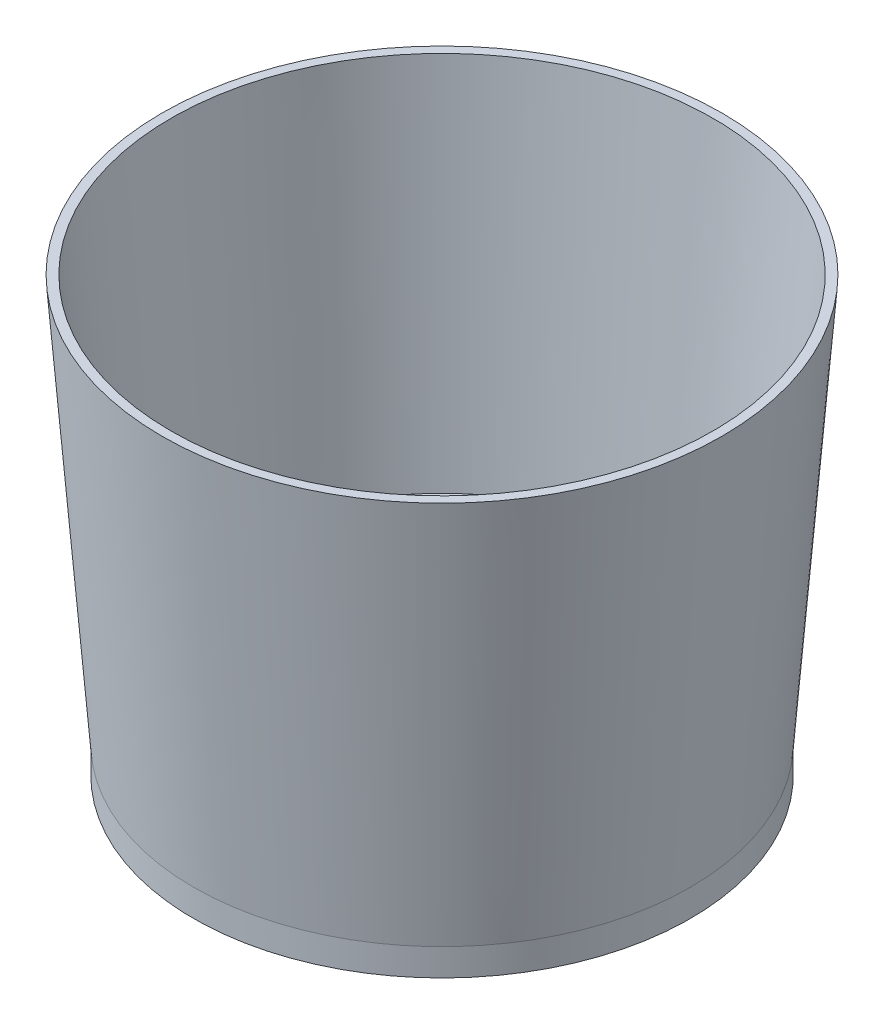
SolidWorks part; units mm, degrees
note: The reader was unsure of these and kept them because the rebuilt part matched: shared geometry of "Sketch3<4>", "Sketch1<4>".
ref_plane "Front Plane" through (0, 0, 0) normal (0, 0, 1) x (1, 0, 0)
ref_plane "Top Plane" through (0, 0, 0) normal (0, 1, 0) x (1, 0, 0)
ref_plane "Right Plane" through (0, 0, 0) normal (1, 0, 0) x (0, 0, -1)
sketch "Sketch1" plane through (0, 0, 0) normal (0, 1, 0) x (1, 0, 0)
  circle A0 centre (0, 0) radius 26.5
  circle A1 centre (0, 0) radius 25.5 construction
  circle A2 centre (0, 0) radius 27.5
  dimension "D1" = 53
  dimension "D2" = 51
  dimension "D3" = 55
ref_plane "Plane1" through (0, 45, 0) normal (0, 1, 0) x (1, 0, 0)
sketch "Sketch3" plane through (0, 45, 0) normal (0, 1, 0) x (1, 0, 0)
  circle A0 centre (0, 0) radius 30
  circle A1 centre (0, 0) radius 31
  dimension "D1" = 60
  dimension "D2" = 62
loft "Loft1" add section "Sketch1" section "Sketch3"
loft "Cut-Loft1" cut section "Sketch3<4>" section "Sketch1<4>"
sketch "Sketch3<4>" plane through (0, 45, 0) normal (0, 1, 0) x (1, 0, 0) same geometry as "Sketch3"
sketch "Sketch1<4>" plane through (0, 0, 0) normal (0, 1, 0) x (1, 0, 0) same geometry as "Sketch1"
sketch "Sketch4" plane through (0, 0, 0) normal (0, -1, 0) x (1, 0, 0)
  circle A0 centre (0, 0) radius 27.5
  circle A1 centre (0, 15) radius 1.5
  circle A2 centre (15, 0) radius 1.5
  circle A3 centre (0, -15) radius 1.5
  circle A4 centre (-15, 0) radius 1.5
  point P15 (0, 0)
  dimension "D1" = 55
  dimension "D2" = 3
  dimension "D4" = 15
  dimension "D3" = 4
extrude "Boss-Extrude1" add sketch "Sketch4" along normal blind 3
sketch "Sketch6" plane through (0, 0, 0) normal (0, 1, 0) x (1, 0, 0)
  circle A0 centre (0, 0) radius 25.5
  circle A1 centre (0, 15) radius 1.5
  circle A2 centre (15, 0) radius 1.5
  circle A3 centre (0, -15) radius 1.5
  circle A4 centre (-15, 0) radius 1.5
  point P15 (0, 0)
  dimension "D1" = 51
  dimension "D2" = 3
  dimension "D3" = 4
extrude "Boss-Extrude2" add sketch "Sketch6" along normal blind 6
sketch "Sketch7" plane through (0, 6, 0) normal (0, 1, 0) x (1, 0, 0)
  circle A0 centre (0, 15) radius 3.5
  circle A1 centre (15, 0) radius 3.5
  circle A2 centre (0, -15) radius 3.5
  circle A3 centre (-15, 0) radius 3.5
  point P12 (0, 0)
  dimension "D1" = 7
  dimension "D2" = 4
extrude "Cut-Extrude1" cut sketch "Sketch7" against normal blind 3
